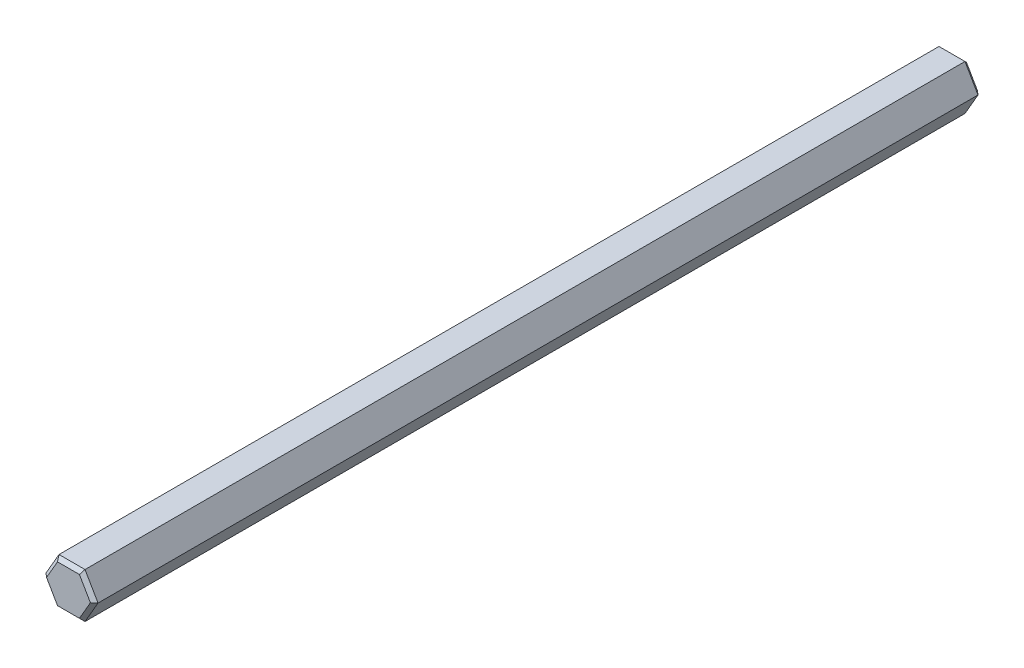
SolidWorks part; units mm, degrees
ref_plane "Front Plane" through (0, 0, 0) normal (0, 0, 1) x (1, 0, 0)
ref_plane "Top Plane" through (0, 0, 0) normal (0, 1, 0) x (1, 0, 0)
ref_plane "Right Plane" through (0, 0, 0) normal (1, 0, 0) x (0, 0, -1)
sketch "Sketch1" plane through (0, 0, 0) normal (0, 0, 1) x (1, 0, 0)
  line L1 (3.6662, 0) -> (1.8331, 3.175)
  line L2 (1.8331, 3.175) -> (-1.8331, 3.175)
  line L3 (-1.8331, 3.175) -> (-3.6662, 0)
  line L4 (-3.6662, 0) -> (-1.8331, -3.175)
  line L5 (-1.8331, -3.175) -> (1.8331, -3.175)
  line L6 (1.8331, -3.175) -> (3.6662, 0)
  circle A0 centre (0, 0) radius 3.175 construction
  point P1 (0, 0)
  dimension "D1" = 6.35
extrude "Boss-Extrude1" add sketch "Sketch1" along normal mid plane 125
ref_axis "Axis1" through (0, 0, -41.25) along (0, 0, 1)
chamfer "Chamfer1" distance 0.5 angle 45 12 edges at (2.7496, 1.5875, -62.5) (0, 3.175, -62.5) (-2.7496, 1.5875, -62.5) (-2.7496, -1.5875, -62.5) (0, -3.175, -62.5) (2.7496, -1.5875, -62.5) (0, -3.175, 62.5) (-2.7496, -1.5875, 62.5) (-2.7496, 1.5875, 62.5) (0, 3.175, 62.5) (2.7496, 1.5875, 62.5) (2.7496, -1.5875, 62.5)
